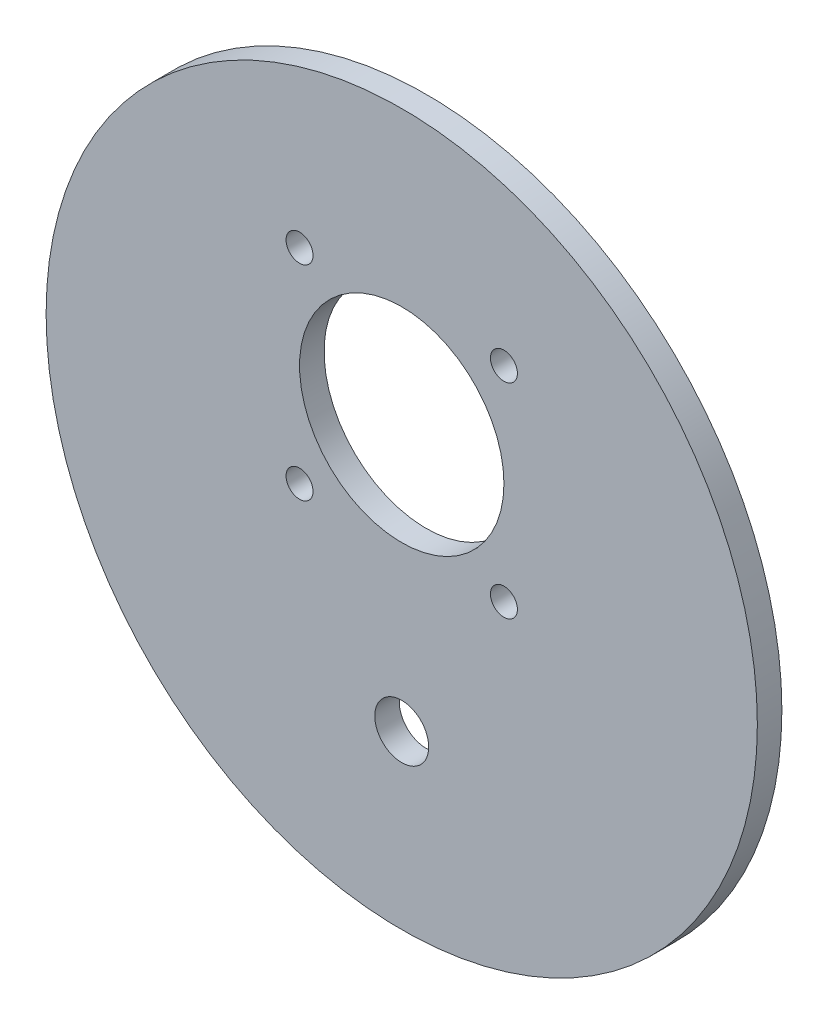
SolidWorks part; units mm, degrees
ref_plane "Front Plane" through (0, 0, 0) normal (0, 0, 1) x (1, 0, 0)
ref_plane "Top Plane" through (0, 0, 0) normal (0, 1, 0) x (1, 0, 0)
ref_plane "Right Plane" through (0, 0, 0) normal (1, 0, 0) x (0, 0, -1)
sketch "Sketch1" plane through (0, 0, 0) normal (0, 0, 1) x (1, 0, 0)
  circle A0 centre (0, 0) radius 43.5 construction
  circle A1 centre (0, 0) radius 43.5
  circle A2 centre (12.5, 22.5) radius 2.15 construction
  circle A3 centre (-12.5, 22.5) radius 2.15 construction
  circle A4 centre (12.5, -2.5) radius 2.15 construction
  circle A5 centre (-12.5, -2.5) radius 2.15 construction
  circle A6 centre (12.5, 22.5) radius 2.15 construction
  circle A7 centre (-12.5, 22.5) radius 2.15 construction
  circle A8 centre (12.5, -2.5) radius 2.15 construction
  circle A9 centre (-12.5, -2.5) radius 2.15 construction
  circle A10 centre (-12.5, -2.5) radius 1.65
  circle A11 centre (12.5, -2.5) radius 1.65
  circle A12 centre (12.5, 22.5) radius 1.65
  circle A13 centre (-12.5, 22.5) radius 1.65
  circle A14 centre (0, 10) radius 12.5 construction
  circle A15 centre (0, 10) radius 12.5
  dimension "D1" = 3.3
extrude "Boss-Extrude1" add sketch "Sketch1" along normal blind 3
sketch "Sketch2" plane through (0, 0, 3) normal (0, 0, 1) x (1, 0, 0)
  circle A2 centre (0, -22.5) radius 3.3
  circle A3 centre (0, -22.5) radius 3.3
  dimension "D1" = 0.3
extrude "Cut-Extrude1" cut sketch "Sketch2" against normal through all both and the other way through all
